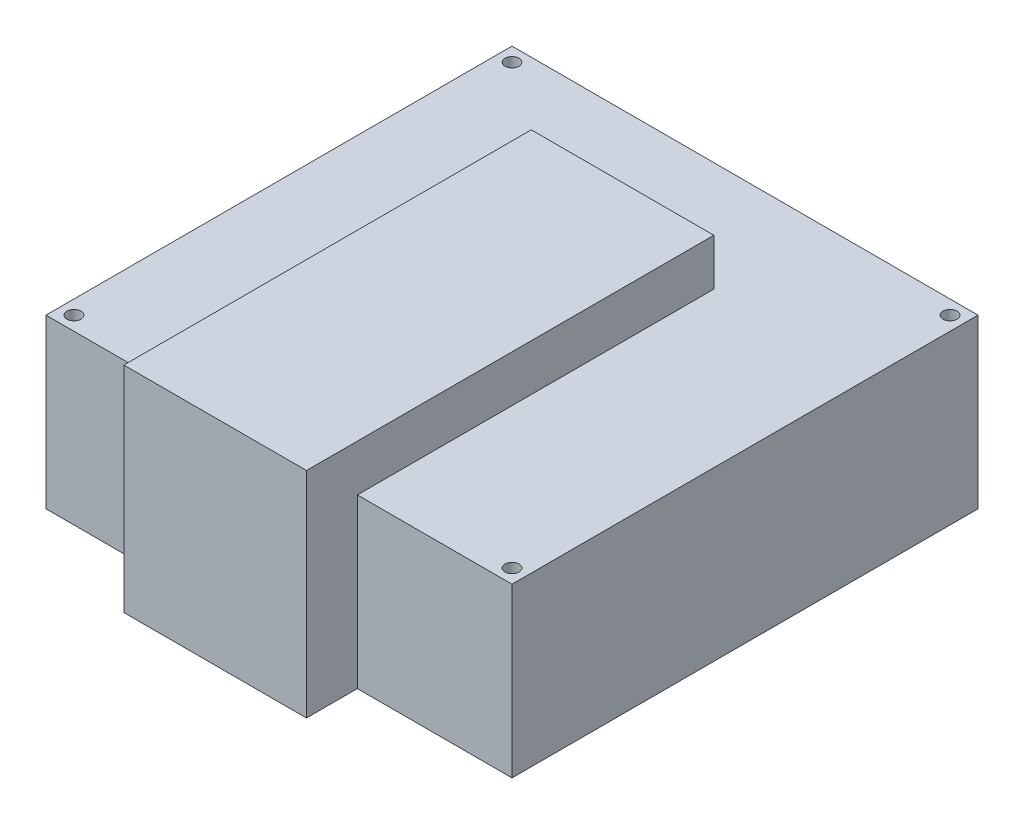
SolidWorks part; units mm, degrees
ref_plane "Front Plane" through (0, 0, 0) normal (0, 0, 1) x (1, 0, 0)
ref_plane "Top Plane" through (0, 0, 0) normal (0, 1, 0) x (1, 0, 0)
ref_plane "Right Plane" through (0, 0, 0) normal (1, 0, 0) x (0, 0, -1)
sketch "Sketch1" plane through (0, 0, 0) normal (0, 1, 0) x (1, 0, 0)
  line L1 (0, 0) -> (100, 0)
  line L2 (0, 0) -> (0, 100)
  line L3 (0, 100) -> (100, 100)
  line L4 (100, 0) -> (100, 100)
  dimension "D1" = 100
  dimension "D2" = 100
extrude "Boss-Extrude1" add sketch "Sketch1" along normal blind 46
sketch "Sketch2" plane through (0, 46, 0) normal (0, 1, 0) x (1, 0, 0)
  line L0 (0, 0) -> (100, 0) construction
  line L1 (66.819, 0) -> (27.6267, 0)
  line L2 (66.819, 0) -> (66.819, 76.5035)
  line L3 (66.819, 76.5035) -> (27.6267, 76.5035)
  line L4 (27.6267, 0) -> (27.6267, 76.5035)
  line L6 (0, 0) -> (100, 0)
  line L7 (0, 0) -> (0, 100)
  line L8 (0, 100) -> (100, 100)
  line L9 (100, 0) -> (100, 100)
  line M1 (0, 100) -> (0, 0)
  line M2 (0, 0) -> (100, 0)
  line M3 (100, 0) -> (100, 100)
  line M4 (100, 100) -> (0, 100)
extrude "Cut-Extrude1" cut sketch "Sketch2" against normal blind 10 contours L4 L3 L2 M2 M3 M4 M1 region at (68.2332, 46, -38.2517)
sketch "Sketch3" plane through (0, 0, 0) normal (0, -1, 0) x (1, 0, 0)
  line L0 (100, -100) -> (0, 0) construction
  line L2 (3, -3) -> (97, -3) construction
  line L3 (3, -3) -> (3, -97) construction
  line L4 (0, 0) -> (0, -100)
  line L5 (0, -100) -> (100, -100)
  line L6 (100, -100) -> (100, 0)
  line L7 (100, 0) -> (0, 0)
  line L8 (0, 0) -> (0, -100) construction
  line L9 (0, -100) -> (100, -100) construction
  line L10 (100, -100) -> (100, 0) construction
  line L11 (100, 0) -> (0, 0) construction
  line L12 (3, -97) -> (97, -97) construction
  line L13 (97, -3) -> (97, -97) construction
  line L14 (3, -3) -> (97, -97) construction
  line L15 (3, -97) -> (97, -3) construction
  circle A0 centre (97, -97) radius 1.5
  circle A1 centre (3, -97) radius 1.5
  circle A2 centre (3, -3) radius 1.5
  circle A3 centre (97, -3) radius 1.5
  point P2 (50, -50)
  dimension "D4" = 3
  dimension "D2" = 94
  dimension "D3" = 94
  dimension "D1" = 0
extrude "Cut-Extrude2" cut sketch "Sketch3" against normal through all
sketch "Sketch4" plane through (0, 0, 0) normal (0, 0, 1) x (1, 0, 0)
  line L0 (0, 0) -> (100, 0) construction
  line L1 (66.819, 46) -> (27.6267, 46)
  line L2 (66.819, 46) -> (66.819, 0)
  line L3 (66.819, 0) -> (27.6267, 0)
  line L4 (27.6267, 46) -> (27.6267, 0)
extrude "Boss-Extrude2" add sketch "Sketch4" along normal blind 10.922
